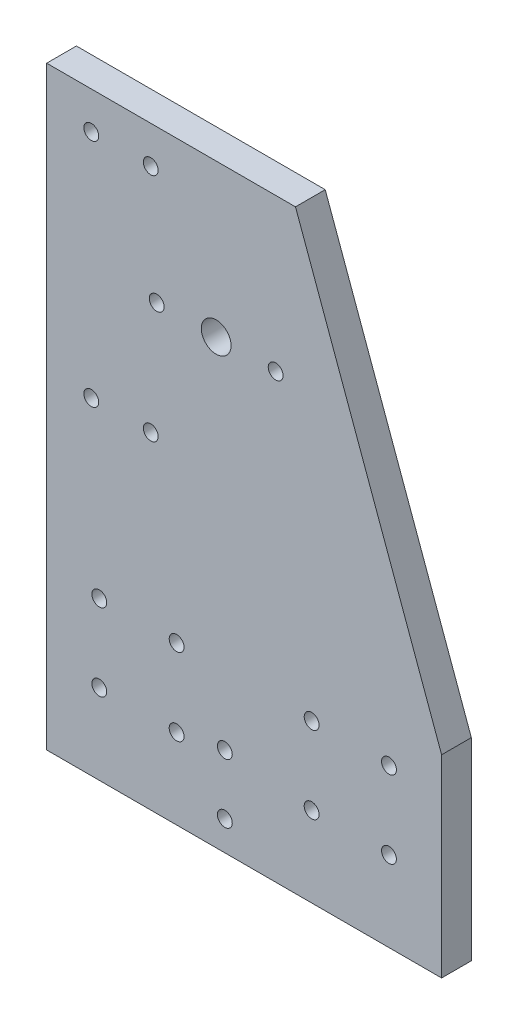
SolidWorks part; units mm, degrees
ref_plane "Front Plane" through (0, 0, 0) normal (0, 0, 1) x (1, 0, 0)
ref_plane "Top Plane" through (0, 0, 0) normal (0, 1, 0) x (1, 0, 0)
ref_plane "Right Plane" through (0, 0, 0) normal (1, 0, 0) x (0, 0, -1)
sketch "Sketch1" plane through (0, 0, 0) normal (0, 0, 1) x (1, 0, 0)
  line L0 (66.4, -5.8678) -> (66.4, 56.1407) construction
  line L5 (0, 0) -> (132.8, 0)
  line L6 (0, 0) -> (0, 200)
  line L7 (0, 200) -> (83.664, 200)
  line L8 (132.8, 0) -> (132.8, 65)
  line L9 (71.4, 57.9012) -> (71.4, -9.8319) construction
  line L23 (102.1, 57.9012) -> (102.1, -7.5742) construction
  line L24 (83.9369, 40) -> (119.8285, 40) construction
  line L25 (52.3456, 19.92) -> (67.8875, 19.92) construction
  line L26 (64.535, 29.92) -> (62.2225, 33.9254)
  line L27 (62.2225, 33.9254) -> (57.5975, 33.9254)
  line L28 (57.5975, 33.9254) -> (55.285, 29.92)
  line L29 (55.285, 29.92) -> (57.5975, 25.9146)
  line L30 (57.5975, 25.9146) -> (62.2225, 25.9146)
  line L31 (62.2225, 25.9146) -> (64.535, 29.92)
  line L32 (62.2225, 13.9254) -> (64.535, 9.92)
  line L33 (57.5975, 13.9254) -> (62.2225, 13.9254)
  line L34 (55.285, 9.92) -> (57.5975, 13.9254)
  line L35 (57.5975, 5.9146) -> (55.285, 9.92)
  line L36 (62.2225, 5.9146) -> (57.5975, 5.9146)
  line L37 (64.535, 9.92) -> (62.2225, 5.9146)
  line L38 (132.8, 65) -> (83.664, 200)
  circle A12 centre (115.1, 27) radius 2.5
  circle A13 centre (89.1, 27) radius 2.5
  circle A14 centre (115.1, 53) radius 2.5
  circle A15 centre (89.1, 53) radius 2.5
  circle A16 centre (17.7, 53) radius 2.5
  circle A17 centre (17.7, 27) radius 2.5
  circle A18 centre (43.7, 27) radius 2.5
  circle A19 centre (43.7, 53) radius 2.5
  circle A20 centre (59.91, 29.92) radius 4.0054 construction
  circle A21 centre (59.91, 29.92) radius 2.5
  circle A23 centre (59.91, 9.92) radius 2.5
  dimension "D4" = 5
  dimension "D13" = 5
  dimension "D1" = 200
  dimension "D2" = 132.8
  dimension "D3" = 26
  dimension "D5" = 61.4
  dimension "D6" = 30.7
  dimension "D7" = 27
  dimension "D8" = 13
  dimension "D9" = 29.92
  dimension "D10" = 10
  dimension "D11" = 9.25
  dimension "D12" = 11.49
  dimension "D14" = 65
  dimension "D15" = 20
  dimension "D16" = 9.92
extrude "Boss-Extrude1" add sketch "Sketch1" along normal blind 10 contours L8 L38 L7 L6 L5 A19 A17 A16 A14 A13 A12 L32 L37 L36 L35 L34 L33 L31 L30 L29 L28 L27 L26 A15 A18 | L30 L31 L26 L27 L28 L29 A21 | L37 L32 L33 L34 L35 L36 region at (59.2103, 92.8578, 0) region at (63.2728, 27.9785, 0) region at (63.2728, 11.8615, 0)
extrude "Cut-Extrude1" cut sketch "Sketch1<3>" along normal blind 5 contours L30 L31 L26 L27 L28 L29 A21 | L37 L32 L33 L34 L35 L36 region at (63.2728, 27.9785, 0) region at (63.2728, 11.8615, 0)
sketch "Sketch1<3>" plane through (0, 0, 0) normal (0, 0, 1) x (1, 0, 0) same geometry as "Sketch1"
sketch "Sketch2" plane through (0, 0, 0) normal (0, 0, -1) x (-1, 0, 0)
  line L9 (0, 200) -> (-83.664, 200) construction
  line L10 (0, 0) -> (0, 200) construction
  circle A0 centre (-35, 187.5) radius 2.5
  circle A1 centre (-15, 187.5) radius 2.5
  circle A2 centre (-35, 110) radius 2.5
  circle A3 centre (-15, 110) radius 2.5
  circle A4 centre (-57, 148.75) radius 5
  circle A6 centre (-77, 148.75) radius 2.5
  circle A7 centre (-37, 148.75) radius 2.5
  dimension "D2" = 5
  dimension "D7" = 10
  dimension "D10" = 5
  dimension "D1" = 20
  dimension "D4" = 15
  dimension "D5" = 2
  dimension "D6" = 77.5
  dimension "D3" = 12.5
  dimension "D8" = 57
  dimension "D9" = 38.75
  dimension "D11" = 40
  dimension "D12" = 20
extrude "Cut-Extrude2" cut sketch "Sketch2" against normal through all
